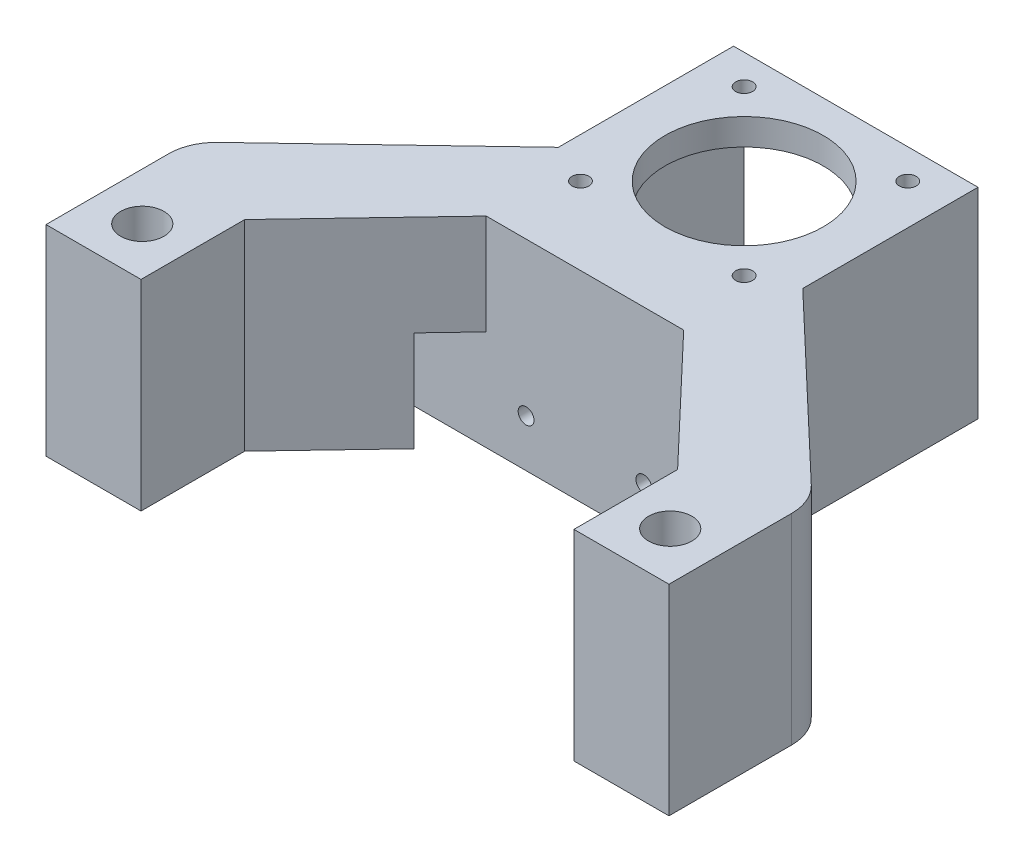
SolidWorks part; units mm, degrees
note: The reader was unsure of these and kept them because the rebuilt part matched: shared geometry of "草图7<7>", "草图7<8>".
ref_plane "前视基准面" through (0, 0, 0) normal (0, 0, 1) x (1, 0, 0)
ref_plane "上视基准面" through (0, 0, 0) normal (0, 1, 0) x (1, 0, 0)
ref_plane "右视基准面" through (0, 0, 0) normal (1, 0, 0) x (0, 0, -1)
sketch "草图6" plane through (0, 0, 0) normal (0, 1, 0) x (1, 0, 0)
  line L1 (-21.15, -21.15) -> (21.15, -21.15)
  line L2 (-21.15, -21.15) -> (-21.15, 21.15)
  line L3 (-21.15, 21.15) -> (21.15, 21.15)
  line L5 (0, 21.15) -> (0, -21.15) construction
  line L6 (-21.15, 0) -> (21.15, 0) construction
  line L8 (21.15, 21.15) -> (21.15, -21.15)
  circle A0 centre (15.5, 15.5) radius 1.6
  circle A1 centre (-15.5, 15.5) radius 1.6
  circle A2 centre (-15.5, -15.5) radius 1.6
  circle A3 centre (15.5, -15.5) radius 1.6
  circle A4 centre (0, 0) radius 15
  point P0 (0, 0)
extrude "凸台-拉伸1" add sketch "草图6" along normal blind 5
sketch "草图7" plane through (0, 5, 0) normal (0, 1, 0) x (1, 0, 0)
  line L0 (0, 0) -> (0, -64)
  line L1 (-59, -65.2381) -> (-59, -73.2381)
  line L2 (21, -10) -> (56.2023, -43.4784)
  line L3 (59, -50) -> (59, -65)
  line L4 (-10, -21) -> (-41, -53.5963)
  line L5 (-21, -10) -> (-56.2023, -43.4784)
  line L6 (10, -21) -> (41, -53.5963)
  line L7 (-59, -73.2381) -> (-41, -73.2381)
  line L8 (41, -53.5963) -> (41, -65)
  line L9 (-41, -73.2381) -> (-41, -65)
  line L10 (-41, -53.5963) -> (-41, -65)
  line L11 (41, -65) -> (41, -73.2381)
  line L12 (-59, -50) -> (-59, -65.2381)
  line L13 (41, -73.2381) -> (59, -73.2381)
  line L14 (59, -73.2381) -> (59, -65)
  arc A0 (-56.2023, -43.4784) -> (-59, -50) centre (-50, -50) ccw
  arc A1 (59, -50) -> (56.2023, -43.4784) centre (50, -50) ccw
  circle A2 centre (-50, -64) radius 4.1
  circle A3 centre (50, -64) radius 4.1
  dimension "D1" = 18
  dimension "D2" = 18
  dimension "D3" = 64
  dimension "D4" = 8.2
  dimension "D5" = 8.2
  dimension "D6" = 8
extrude "凸台-拉伸5" add sketch "草图7" against normal blind 38
extrude "凸台-拉伸7" add sketch "草图7<7>" against normal blind 38
sketch "草图7<7>" plane through (0, 5, 0) normal (0, 1, 0) x (1, 0, 0) same geometry as "草图7"
extrude "凸台-拉伸8" add sketch "草图7<8>" against normal blind 38 contours A0 A3
sketch "草图7<8>" plane through (0, 5, 0) normal (0, 1, 0) x (1, 0, 0) same geometry as "草图7"
sketch "草图12" plane through (0, 5, 0) normal (0, 1, 0) x (1, 0, 0)
  line L0 (21.15, 21.15) -> (23.15, 21.15)
  line L1 (21.15, 21.15) -> (21.15, -23.15)
  line L2 (23.15, 21.15) -> (23.15, -23.15)
  line L3 (21.15, -23.15) -> (23.15, -23.15)
extrude "凸台-拉伸11" add sketch "草图12" against normal blind 38
sketch "草图14" plane through (0, 5, 0) normal (0, 1, 0) x (1, 0, 0)
  line L0 (21.15, -23.15) -> (-23.15, -23.15)
  line L1 (21.15, -23.15) -> (21.15, -21.15)
  line L2 (-23.15, -23.15) -> (-23.15, -21.15)
  line L3 (21.15, -21.15) -> (-23.15, -21.15)
extrude "凸台-拉伸12" add sketch "草图14" against normal blind 38
sketch "草图15" plane through (0, 5, 0) normal (0, 1, 0) x (1, 0, 0)
  line L0 (-23.15, -21.15) -> (-23.15, 21.15)
  line L1 (-23.15, -21.15) -> (-21.15, -21.15)
  line L2 (-23.15, 21.15) -> (-21.15, 21.15)
  line L3 (-21.15, -21.15) -> (-21.15, 21.15)
extrude "凸台-拉伸13" add sketch "草图15" against normal blind 38
sketch "草图17" plane through (0, -33, 0) normal (0, -1, 0) x (1, 0, 0)
  line L3 (61.1203, 30.15) -> (-61.8372, 30.15)
  line L6 (61.1203, 30.15) -> (61.1203, 37.15)
  line L7 (61.1203, 37.15) -> (-61.8372, 37.15)
  line L8 (-61.8372, 37.15) -> (-61.8372, 30.15)
  dimension "D1" = 7
extrude "切除-拉伸1" cut sketch "草图17" against normal blind 19
sketch "草图20" plane through (0, 0, 21.15) normal (0, 0, -1) x (-1, 0, 0)
  line L1 (-21.15, -33) -> (-21.15, 0) construction
  line L2 (21.15, -33) -> (21.15, 0) construction
  line L4 (-7.75, -24) -> (-9.45, -21.0555)
  line L5 (-9.45, -21.0555) -> (-12.85, -21.0555)
  line L6 (-12.85, -21.0555) -> (-14.55, -24)
  line L7 (-14.55, -24) -> (-12.85, -26.9445)
  line L8 (-12.85, -26.9445) -> (-9.45, -26.9445)
  line L9 (-9.45, -26.9445) -> (-7.75, -24)
  line L10 (14.55, -24) -> (12.85, -21.0555)
  line L11 (12.85, -21.0555) -> (9.45, -21.0555)
  line L12 (9.45, -21.0555) -> (7.75, -24)
  line L13 (7.75, -24) -> (9.45, -26.9445)
  line L14 (9.45, -26.9445) -> (12.85, -26.9445)
  line L15 (12.85, -26.9445) -> (14.55, -24)
  circle A2 centre (-11.15, -24) radius 2.9445 construction
  circle A3 centre (11.15, -24) radius 2.9445 construction
  dimension "D3" = 10
  dimension "D4" = 10
  dimension "D5" = 3.4
  dimension "D6" = 3.4
sketch "草图21" plane through (0, -33, 0) normal (0, -1, 0) x (1, 0, 0)
  line L0 (18.7019, 30.15) -> (-18.7019, 30.15)
  line L1 (-18.7019, 30.15) -> (-12.0447, 23.15)
  line L2 (-12.0447, 23.15) -> (12.0447, 23.15)
  line L3 (12.0447, 23.15) -> (18.7019, 30.15)
extrude "凸台-拉伸14" add sketch "草图21" against normal blind 38
extrude "切除-拉伸3" cut sketch "草图20" against normal blind 3
sketch "草图22" plane through (0, 0, 21.15) normal (0, 0, -1) x (-1, 0, 0)
  line L0 (21.15, -33) -> (21.15, 0) construction
  line L1 (21.15, -33) -> (-21.15, -33) construction
  line L2 (-21.15, -33) -> (-21.15, 0) construction
  circle A0 centre (11.15, -24) radius 1.5
  circle A1 centre (-11.15, -24) radius 1.5
  dimension "D1" = 10
  dimension "D2" = 9
  dimension "D3" = 10
  dimension "D4" = 9
extrude "切除-拉伸4" cut sketch "草图22" against normal blind 10
